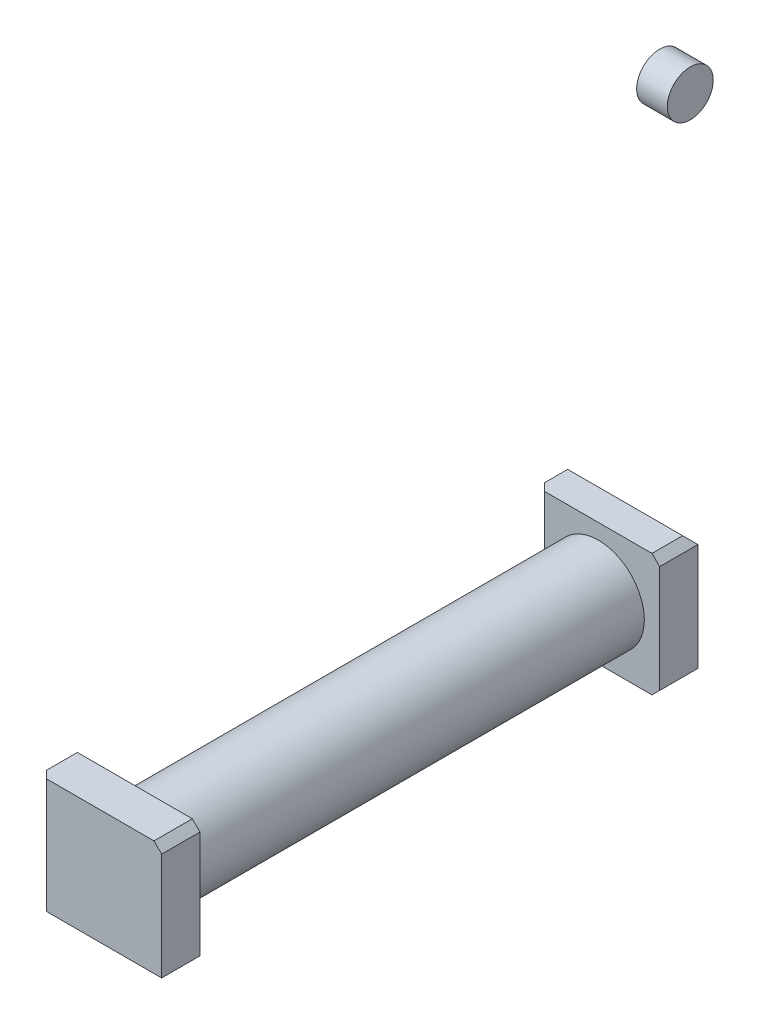
SolidWorks part; units mm, degrees
ref_plane "前视基准面" through (0, 0, 0) normal (0, 0, 1) x (1, 0, 0)
ref_plane "上视基准面" through (0, 0, 0) normal (0, 1, 0) x (1, 0, 0)
ref_plane "右视基准面" through (0, 0, 0) normal (1, 0, 0) x (0, 0, -1)
other "Configuration Table"
sketch "Sketch1" plane through (0, 0, 0) normal (0, 0, 1) x (1, 0, 0)
  circle A0 centre (0, 0) radius 30
extrude "Boss-Extrude1" add sketch "Sketch1" along normal blind 300
sketch "Sketch2" plane through (0, 0, 0) normal (0, 0, 1) x (1, 0, 0)
  line L1 (-40, -40) -> (40, -40)
  line L2 (-40, -40) -> (-40, 40)
  line L3 (-40, 40) -> (40, 40)
  line L4 (40, -40) -> (40, 40)
  line L5 (-40, -40) -> (40, 40) construction
  line L6 (-40, 40) -> (40, -40) construction
  point P0 (0, 0)
extrude "Boss-Extrude2" add sketch "Sketch2" against normal blind 25
sketch "Sketch3" plane through (0, 0, 0) normal (0, 0, 1) x (1, 0, 0)
  circle A0 centre (0, 0) radius 21
extrude "Cut-Extrude1" cut sketch "Sketch3" against normal blind 30
ref_plane "Plane1" through (0, 0, 300) normal (0, 0, 1) x (1, 0, 0)
sketch "Sketch4" plane through (0, 0, 300) normal (0, 0, 1) x (1, 0, 0)
  line L1 (-40, -40) -> (40, -40)
  line L2 (-40, -40) -> (-40, 40)
  line L3 (-40, 40) -> (40, 40)
  line L4 (40, -40) -> (40, 40)
  line L5 (-40, -40) -> (40, 40) construction
  line L6 (-40, 40) -> (40, -40) construction
  point P0 (0, 0)
extrude "Boss-Extrude3" add sketch "Sketch4" along normal blind 25
ref_plane "Plane2" through (40, 0, 0) normal (1, 0, 0) x (0, 0, -1)
sketch "Sketch5" plane through (40, 0, 0) normal (1, 0, 0) x (0, 0, -1)
  circle A0 centre (0, 312.5) radius 15
extrude "Boss-Extrude4" add sketch "Sketch5" along normal blind 20
chamfer "Chamfer1" distance 5 angle 45 4 edges at (40, -40, -12.5) (-40, 0, 0) (0, 40, -25) (40, 40, -12.5)
chamfer "Chamfer3" distance 5 angle 45 4 edges at (40, -40, 312.5) (0, -40, 325) (-40, 0, 325) (40, 40, 312.5)
ref_plane "link1_bottom_face" through (0, 0, 0) normal (0, 0, 1) x (1, 0, 0)
sketch3d "3DSketch1"
  line L0 (0, 0, -100) -> (0, 0, 100) construction
ref_axis "link1_bottom_hole_axis" through (0, 0, -100) along (0, 0, 1)
ref_plane "link1_top_side_face_pin_base" through (40, 0, 0) normal (1, 0, 0) x (0, 0, -1)
sketch3d "3DSketch2"
  line L0 (40, 0, 312.5) -> (60, 0, 312.5) construction
ref_axis "link1_top_pin_axis" through (40, 0, 312.5) along (1, 0, 0)
